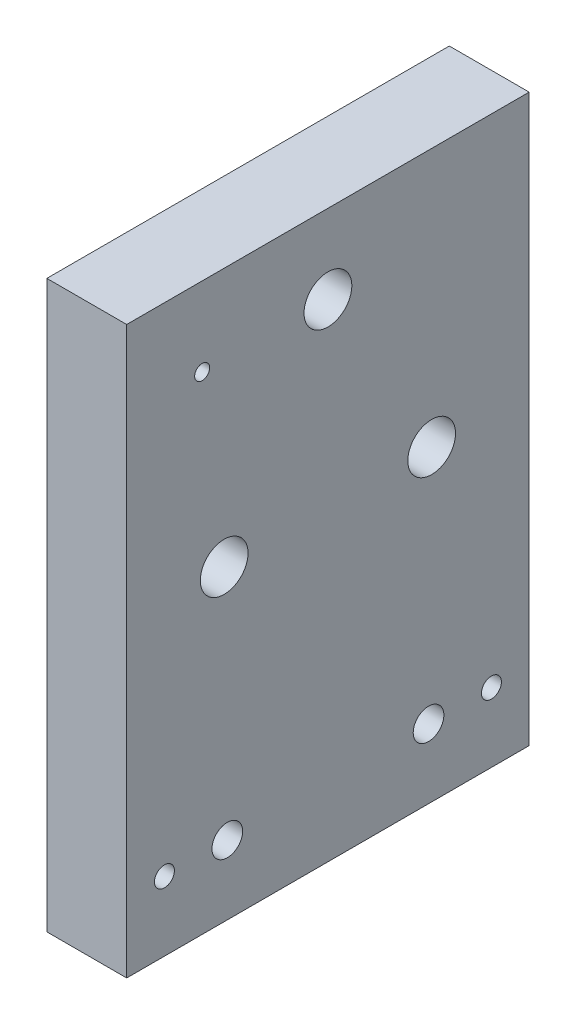
SolidWorks part; units mm, degrees
material "6061-T4 (SS)"
ref_plane "Front Plane" through (0, 0, 0) normal (0, 0, 1) x (1, 0, 0)
ref_plane "Top Plane" through (0, 0, 0) normal (0, 1, 0) x (1, 0, 0)
ref_plane "Right Plane" through (0, 0, 0) normal (1, 0, 0) x (0, 0, -1)
sketch "Sketch1" plane through (0, 0, 0) normal (0, 1, 0) x (1, 0, 0)
  line L1 (-36.5, 16) -> (36.5, 16)
  line L2 (-36.5, 16) -> (-36.5, -16)
  line L3 (-36.5, -16) -> (36.5, -16)
  line L4 (36.5, 16) -> (36.5, -16)
  line L5 (-36.5, 16) -> (36.5, -16) construction
  line L6 (-36.5, -16) -> (36.5, 16) construction
  point P0 (0, 0)
  dimension "D1" = 73
  dimension "D2" = 32
sketch "Sketch26" plane through (0, 0, 0) normal (0, 1, 0) x (-1, 0, 0)
  line L1 (-6.35, 0) -> (0, 0)
  line L2 (-6.35, 0) -> (-6.35, 32)
  line L3 (-6.35, 32) -> (0, 32)
  line L4 (0, 0) -> (0, 32)
  dimension "D1" = 6.35
  dimension "D2" = 32
extrude "Boss-Extrude2" add sketch "Sketch26" along normal blind 45
sketch "Sketch27" plane through (0, 0, 0) normal (-1, 0, 0) x (0, 0, 1)
  line L0 (32, 45) -> (0, 45) construction
  line L1 (0, 45) -> (0, 0) construction
  line L3 (7.7511, 24.4375) -> (24.2489, 24.4375) construction
  line L4 (16, 24.4375) -> (16, 38.725) construction
  line L5 (7.7511, 24.4375) -> (32, 24.4375) construction
  line L7 (24.2489, 24.4375) -> (0, 24.4375) construction
  line L9 (32, 45) -> (32, 0) construction
  circle A0 centre (16, 38.725) radius 1.595
  circle A1 centre (24.2489, 24.4375) radius 1.595
  circle A2 centre (7.7511, 24.4375) radius 1.595
  dimension "D1" = 3.19
  dimension "D2" = 3.19
  dimension "D3" = 3.19
  dimension "D6" = 14.2875
  dimension "D7" = 16.4978
  dimension "D8" = 6.275
extrude "Cut-Extrude7" cut sketch "Sketch27" against normal up to next
hole_wizard "CBORE for #6 Binding Head Machine Screw1" positions "Sketch57" profile "Sketch58" counterbore size "#6" standard "ANSI Inch"
sketch "Sketch57" plane through (0, 0, 0) normal (-1, 0, 0) x (0, 0, 1)
  point P0 (16, 38.725)
  point P3 (24.2489, 24.4375)
  point P6 (7.7511, 24.4375)
sketch "Sketch58" plane through (0, 38.725, 16) normal (0, 1, 0) x (0, 0, 1)
  line L0 (0, 0) -> (0, 47.6408)
  line L1 (0, 47.6408) -> (1.8986, 46.5)
  line L2 (1.8986, 46.5) -> (1.8986, 1.016)
  line L3 (1.8986, 1.016) -> (4.7625, 1.016)
  line L4 (4.7625, 1.016) -> (4.7625, 0)
  line L5 (4.7625, 0) -> (0, 0)
  line L10 (0, 47.6408) -> (-1.8987, 46.5) construction
  line L11 (0, -6.35) -> (0, 107.95) construction
  dimension "Hole Dia." = 3.7973
  dimension "Hole Depth" = 46.5
  dimension "C'Bore Dia." = 9.525
  dimension "C'Bore Depth" = 1.016
  dimension "Drill Angle" = 118
sketch "Sketch88" plane through (0, 0, 0) normal (-1, 0, 0) x (0, 0, 1)
  line L0 (32, 45) -> (32, 0) construction
  point P0 (32, 22.5)
hole_wizard "#0-80 Tapped Hole1" positions "Sketch93" profile "Sketch94" tap size "#0-80" standard "ANSI Inch" end condition through all
sketch "Sketch93" plane through (0, 0, 0) normal (-1, 0, 0) x (0, 0, 1)
  line L4 (16, 38.725) -> (26, 38.725) construction
  line L5 (26, 38.725) -> (0, 38.725) construction
  line L7 (0, 45) -> (0, 0) construction
  line L8 (32, 45) -> (0, 45) construction
  circle A0 centre (16, 38.725) radius 4.7625 construction
  point P0 (26, 38.725)
  dimension "D1" = 10
  dimension "D2" = 6.275
sketch "Sketch94" plane through (0, 38.725, 26) normal (0, 1, 0) x (0, 0, 1)
  line L0 (0, 0) -> (0, 6.35)
  line L1 (0, 6.35) -> (0.5956, 6.35)
  line L2 (0.5956, 6.35) -> (0.5956, 0)
  line L5 (0.5956, 0) -> (0, 0)
  line L11 (0, -6.35) -> (0, 107.95) construction
  dimension "Thru Tap Drill Dia." = 1.1913
  dimension "Thru Tap Drill Depth" = 6.35
cosmetic thread "Hole Thread1" parameters "D2"=1.524
hole_wizard "#2 Clearance Hole1" positions "Sketch101" profile "Sketch102" hole size "#2" standard "ANSI Inch"
sketch "Sketch101" plane through (0, 0, 0) normal (-1, 0, 0) x (0, 0, 1)
  point P0 (8, 5.5)
  point P3 (24, 5.5)
sketch "Sketch102" plane through (0, 5.5, 8) normal (0, 1, 0) x (0, 0, 1)
  line L0 (0, 0) -> (0, 21.0526)
  line L1 (0, 21.0526) -> (1.2192, 20.32)
  line L2 (1.2192, 20.32) -> (1.2192, 0)
  line L5 (1.2192, 0) -> (0, 0)
  line L10 (0, 21.0526) -> (-1.2192, 20.32) construction
  line L11 (0, -6.35) -> (0, 107.95) construction
  dimension "Hole Dia." = 2.4384
  dimension "Hole Depth" = 20.32
  dimension "Drill Angle" = 118
hole_wizard "1/16 (0.0625) Dowel Hole1" positions "Sketch103" profile "Sketch104" hole size "1/16" standard "ANSI Inch"
sketch "Sketch103" plane through (6.35, 0, 0) normal (1, 0, 0) x (0, 0, -1)
  point P0 (-29, 5.5)
  point P2 (-3, 5.5)
  point P6 (-29, 5.5)
sketch "Sketch104" plane through (6.35, 5.5, 29) normal (0, 1, 0) x (0, 0, -1)
  line L0 (0, 0) -> (0, 4)
  line L1 (0, 4) -> (0.7937, 3.5231)
  line L2 (0.7937, 3.5231) -> (0.7937, 0)
  line L5 (0.7937, 0) -> (0, 0)
  line L10 (0, 4) -> (-0.7938, 3.5231) construction
  line L11 (0, -6.35) -> (0, 107.95) construction
  dimension "Hole Dia." = 1.5875
  dimension "Hole Depth" = 4
  dimension "Drill Angle" = 118
